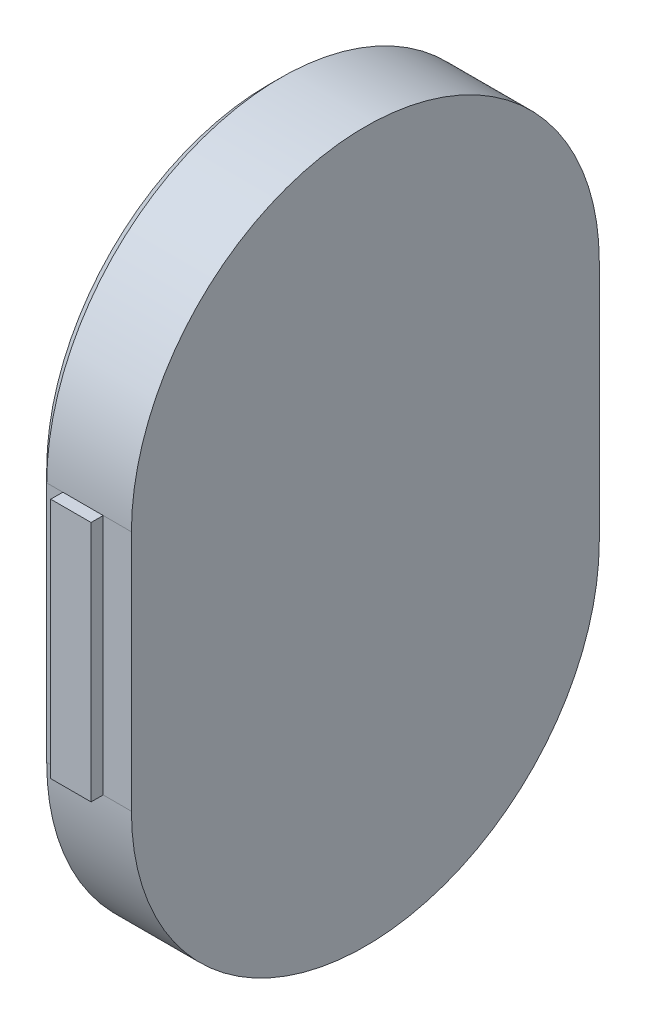
SolidWorks part; units mm, degrees
ref_plane "Front Plane" through (0, 0, 0) normal (0, 0, 1) x (1, 0, 0)
ref_plane "Top Plane" through (0, 0, 0) normal (0, 1, 0) x (1, 0, 0)
ref_plane "Right Plane" through (0, 0, 0) normal (1, 0, 0) x (0, 0, -1)
sketch "Sketch1" plane through (0, 0, 0) normal (1, 0, 0) x (0, 0, -1)
  line L0 (-73.2, 110) -> (-73.2, 116)
  line L1 (-61.6, 116) -> (-61.6, 110)
  arc A0 (-61.6, 110) -> (-67.4, 104.2) centre (-67.4, 110) cw
  arc A1 (-67.4, 104.2) -> (-73.2, 110) centre (-67.4, 110) cw
  arc A2 (-73.2, 116) -> (-67.4, 121.8) centre (-67.4, 116) cw
  arc A3 (-67.4, 121.8) -> (-61.6, 116) centre (-67.4, 116) cw
extrude "Boss-Extrude1" add sketch "Sketch1" along normal blind 2.4 from offset 63 offset against normal yes
chamfer "Chamfer1" distance 0.3 angle 45 4 edges at (-63, 104.2, 67.4) (-63, 113, 61.6) (-63, 113, 73.2) (-63, 121.8, 67.4)
sketch "Sketch2" plane through (0, 0, 0) normal (0, 0, 1) x (1, 0, 0)
  line L1 (-62.3, 110) -> (-61.3, 110)
  line L2 (-62.3, 110) -> (-62.3, 116)
  line L3 (-62.3, 116) -> (-61.3, 116)
  line L4 (-61.3, 110) -> (-61.3, 116)
extrude "Boss-Extrude2" add sketch "Sketch2" along normal blind 0.31 from offset 61.3
sketch "Sketch3" plane through (0, 0, 0) normal (0, 0, 1) x (1, 0, 0)
  line L1 (-62.3, 110) -> (-61.3, 110)
  line L2 (-62.3, 110) -> (-62.3, 116)
  line L3 (-62.3, 116) -> (-61.3, 116)
  line L4 (-61.3, 110) -> (-61.3, 116)
extrude "Boss-Extrude3" add sketch "Sketch3" along normal blind 0.31 from offset 73.19
sketch "Sketch4" plane through (0, 0, 0) normal (0, 0, 1) x (1, 0, 0)
  line L1 (-63.1, 104.1) -> (-62.4, 104.1)
  line L2 (-63.1, 104.1) -> (-63.1, 105.4)
  line L3 (-63.1, 105.4) -> (-62.4, 105.4)
  line L4 (-62.4, 104.1) -> (-62.4, 105.4)
extrude "Boss-Extrude4" add sketch "Sketch4" along normal blind 3 from offset 65.9 separate body
combine bodies "Combine1" operation type subtract main body 103 bodies to subtract 104
